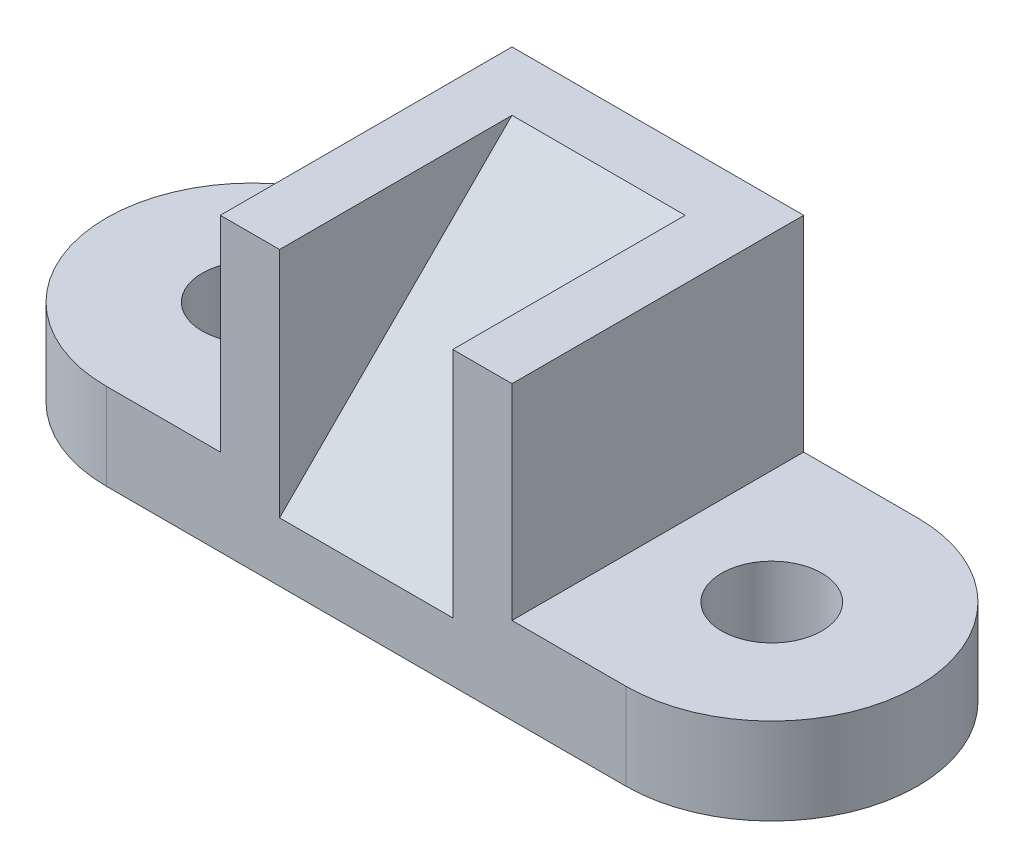
SolidWorks part; units mm, degrees
ref_plane "Front Plane" through (0, 0, 0) normal (0, 0, 1) x (1, 0, 0)
ref_plane "Top Plane" through (0, 0, 0) normal (0, 1, 0) x (1, 0, 0)
ref_plane "Right Plane" through (0, 0, 0) normal (1, 0, 0) x (0, 0, -1)
sketch "Sketch1" plane through (0, 0, 0) normal (0, 1, 0) x (1, 0, 0)
  line L0 (0, 0) -> (114, 0) construction
  line L1 (0, 32) -> (114, 32)
  line L2 (0, -32) -> (114, -32)
  line L3 (25, 32) -> (25, -32)
  line L4 (89, 32) -> (89, -32)
  line L5 (38, -32) -> (38, 19)
  line L6 (38, 19) -> (76, 19)
  line L7 (76, 19) -> (76, -32)
  line L8 (57, 49.6335) -> (57, -36.8326) construction
  arc A0 (0, 32) -> (0, -32) centre (0, 0) ccw
  arc A1 (114, -32) -> (114, 32) centre (114, 0) ccw
  circle A2 centre (0, 0) radius 11
  circle A3 centre (114, 0) radius 11
  point P3 (57, 0)
  dimension "D2" = 32
  dimension "D3" = 22
  dimension "D1" = 114
  dimension "D4" = 64
  dimension "D5" = 38
  dimension "D6" = 13
extrude "Boss-Extrude1" add sketch "Sketch1" along normal blind 19 contours L1 A0 L2 L3 A2 | L2 A1 L1 L4 A3 region at (12.5, 0, -31.143) region at (101.5, 0, -31.143)
extrude "Boss-Extrude2" add sketch "Sketch1<3>" along normal blind 64 contours L6 L7 L2 L4 L1 L3 L5 region at (57, 0, -31.0949)
sketch "Sketch1<3>" plane through (0, 0, 0) normal (0, 1, 0) x (1, 0, 0) same geometry as "Sketch1"
extrude "Boss-Extrude3" add sketch "Sketch1<4>" along normal blind 13 contours L7 L6 L5 L2 region at (57, 0, 6.5)
sketch "Sketch1<4>" plane through (0, 0, 0) normal (0, 1, 0) x (1, 0, 0) same geometry as "Sketch1"
sketch "Sketch3" plane through (38, 0, 0) normal (1, 0, 0) x (0, 0, -1)
  line L0 (19, 64) -> (-32, 13)
  line L1 (19, 64) -> (19, 13) construction
  line L2 (-32, 13) -> (19, 13) construction
  line L3 (19, 64) -> (19, 13)
  line L4 (-32, 13) -> (19, 13)
extrude "Boss-Extrude4" add sketch "Sketch3" along normal up to next contours L0 L4 L3
